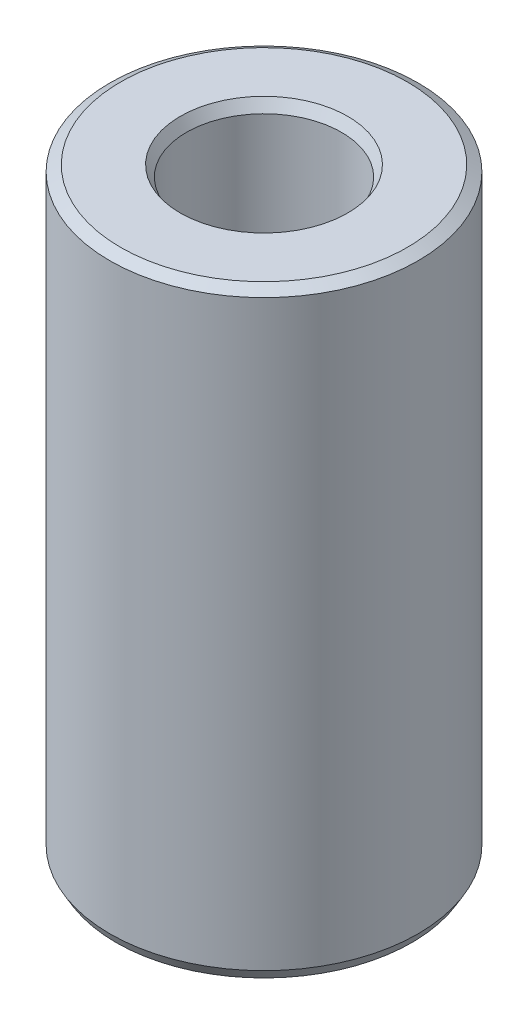
SolidWorks part; units mm, degrees
ref_plane "Front Plane" through (0, 0, 0) normal (0, 0, 1) x (1, 0, 0)
ref_plane "Top Plane" through (0, 0, 0) normal (0, 1, 0) x (1, 0, 0)
ref_plane "Right Plane" through (0, 0, 0) normal (1, 0, 0) x (0, 0, -1)
sketch "Sketch1" plane through (0, 0, 0) normal (0, 1, 0) x (1, 0, 0)
  circle A0 centre (0, 0) radius 52.5
  dimension "SLEEVE_OD" = 105
extrude "Boss-Extrude1" add sketch "Sketch1" along normal blind 204.3517
sketch "Sketch2" plane through (0, 0, 0) normal (0, 1, 0) x (1, 0, 0)
  circle A0 centre (0, 0) radius 26.4269
  dimension "BORE_D" = 52.8539
extrude "Cut-Extrude1" cut sketch "Sketch2" along normal through all
chamfer "Chamfer1" distance 2.1128 angle 60 4 edges at (0, 204.3517, 26.4269) (0, 0, 26.4269) (0, 0, 52.5) (0, 204.3517, 52.5) first distance on face at (0, 204.3517, 26.4269) first distance on face at (0, 0, 26.4269) first distance on face at (0, 204.3517, 52.5)
